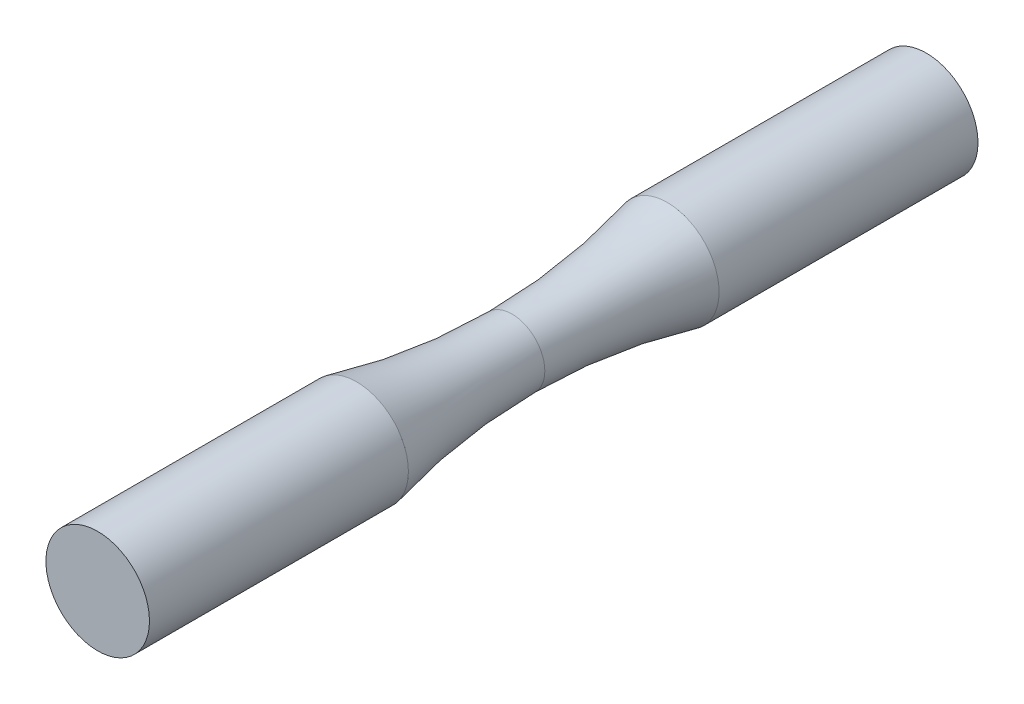
SolidWorks part; units mm, degrees
ref_plane "Front Plane" through (0, 0, 0) normal (0, 0, 1) x (1, 0, 0)
ref_plane "Top Plane" through (0, 0, 0) normal (0, 1, 0) x (1, 0, 0)
ref_plane "Right Plane" through (0, 0, 0) normal (1, 0, 0) x (0, 0, -1)
sketch "Sketch2" plane through (0, 0, 0) normal (0, 0, 1) x (1, 0, 0)
  circle A0 centre (0, 0) radius 6.35
  dimension "D1" = 12.7
extrude "Boss-Extrude1" add sketch "Sketch2" along normal blind 31.75
ref_plane "Plane1" through (0, 0, 31.75) normal (0, 0, 1) x (1, 0, 0)
ref_plane "Plane2" through (0, 0, 50.8) normal (0, 0, 1) x (1, 0, 0)
sketch "Sketch4" plane through (0, 0, 31.75) normal (0, 0, 1) x (1, 0, 0)
  circle A0 centre (0, 0) radius 6.35
  dimension "D1" = 12.7
ref_plane "Plane3" through (0, 0, 69.85) normal (0, 0, 1) x (1, 0, 0)
sketch "Sketch7" plane through (0, 0, 0) normal (1, 0, 0) x (0, 0, -1)
  line L0 (0, 0) -> (-96.9029, 0) construction
  line L1 (-50.8, -4.0323) -> (-50.8, 4.0322)
  line L2 (-69.85, -6.35) -> (-69.85, 6.35)
  line L3 (-31.75, -6.35) -> (-31.75, 6.35)
  arc A0 (-69.85, 6.35) -> (-31.75, 6.35) centre (-50.8, 83.4788) ccw
  point P6 (-50.8, 0)
  point P9 (-69.85, 0)
  point P13 (-31.75, 0)
  dimension "D1" = 8.0645
  dimension "D2" = 12.7
  dimension "D3" = 19.05
  dimension "D4" = 12.7
  dimension "D5" = 19.05
revolve "Revolve1" add sketch "Sketch7" angle 360 about L0 region at (0, 2.4497, 40.5108) region at (0, 2.4497, 61.0892)
sketch "Sketch8" plane through (0, 0, 69.85) normal (0, 0, 1) x (1, 0, 0)
  circle A0 centre (0, 0) radius 6.35
extrude "Boss-Extrude2" add sketch "Sketch8" along normal blind 31.75
ref_axis "Axis1" through (6.985, 0, 0) along (-1, 0, 0)
ref_axis "Axis2" through (-6.985, 0, 101.6) along (1, 0, 0)
ref_plane "Plane4" through (0, 0, 50.8) normal (0, 0, -1) x (-1, 0, 0)
split line "Split Line3"
